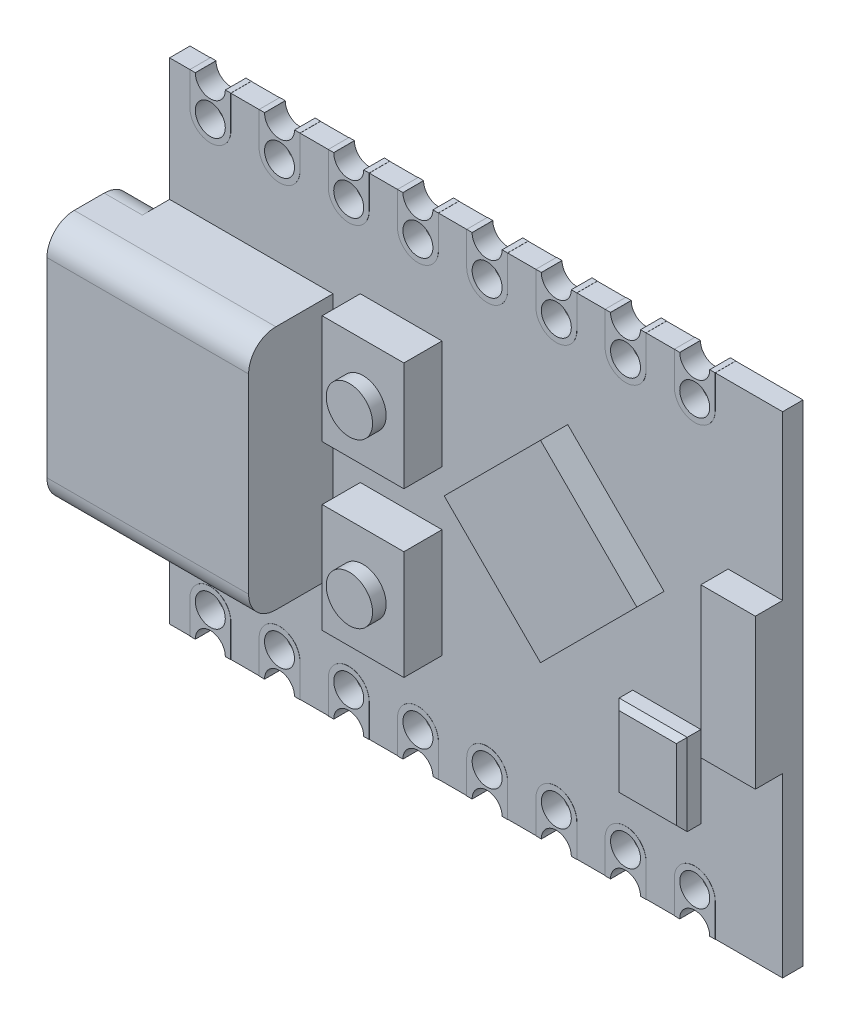
SolidWorks part; units mm, degrees
ref_plane "Plano frontal" through (0, 0, 0) normal (0, 0, 1) x (1, 0, 0)
ref_plane "Plano superior" through (0, 0, 0) normal (0, 1, 0) x (1, 0, 0)
ref_plane "Plano direito" through (0, 0, 0) normal (1, 0, 0) x (0, 0, -1)
sketch "Esboço1" plane through (0, 0, 0) normal (0, 0, 1) x (1, 0, 0)
  line L1 (-22.5, 18) -> (0, 18)
  line L2 (-22.5, 18) -> (-22.5, 0)
  line L3 (-22.5, 0) -> (0, 0)
  line L4 (0, 18) -> (0, 0)
  dimension "D1" = 18
  dimension "D2" = 22.5
extrude "PCI" add sketch "Esboço1" along normal blind 0.75
sketch "Esboço2" plane through (0, 0, 0.75) normal (0, 0, 1) x (1, 0, 0)
  line L0 (-11.4211, 10.1145) -> (-7.8855, 13.65)
  line L1 (-11.4211, 10.1145) -> (-7.8855, 6.5789)
  line L2 (-7.8855, 13.65) -> (-4.35, 10.1145)
  line L3 (-7.8855, 6.5789) -> (-4.35, 10.1145)
  line L4 (0, 0) -> (0, 18) construction
  line L5 (0, 18) -> (-22.5, 18) construction
  dimension "D1" = 45
  dimension "D2" = 4.35
  dimension "D3" = 4.35
  dimension "D4" = 5
extrude "ESP32" add sketch "Esboço2" along normal blind 1
sketch "Esboço3" plane through (0, 0, 0.75) normal (0, 0, 1) x (1, 0, 0)
  line L0 (-22.5, 18) -> (-22.5, 0) construction
  line L1 (-16.5, 13.5) -> (-23.9, 13.5)
  line L2 (-16.5, 13.5) -> (-16.5, 4.5)
  line L3 (-16.5, 4.5) -> (-23.9, 4.5)
  line L4 (-23.9, 13.5) -> (-23.9, 4.5)
  line L5 (-22.5, 9) -> (0, 9) construction
  line L6 (0, 0) -> (0, 18) construction
  dimension "D1" = 1.4
  dimension "D2" = 7.4
  dimension "D3" = 4.5
  dimension "D4" = 9
extrude "USB-C" add sketch "Esboço3" along normal blind 3.1
fillet "Arredondamento inferior USB" radius 1 2 edges at (-23.2, 13.5, 0.75) (-23.2, 4.5, 0.75)
fillet "Arredondamento Superior USB" radius 1 2 edges at (-20.2, 13.5, 3.85) (-20.2, 4.5, 3.85)
sketch "Esboço8" plane through (-23.9, 0, 0) normal (-1, 0, 0) x (0, 0, 1)
  line L0 (1.05, 12.5) -> (1.05, 5.5)
  line L1 (1.75, 4.8) -> (2.85, 4.8)
  line L2 (3.55, 5.5) -> (3.55, 12.5)
  line L3 (2.85, 13.2) -> (1.75, 13.2)
  line L4 (2.85, 13.5) -> (1.75, 13.5) construction
  line L5 (3.85, 12.5) -> (3.85, 5.5) construction
  arc A0 (1.75, 13.2) -> (1.05, 12.5) centre (1.75, 12.5) ccw
  arc A1 (1.05, 5.5) -> (1.75, 4.8) centre (1.75, 5.5) ccw
  arc A2 (2.85, 4.8) -> (3.55, 5.5) centre (2.85, 5.5) ccw
  arc A3 (3.55, 12.5) -> (2.85, 13.2) centre (2.85, 12.5) ccw
  dimension "D1" = 0.7
  dimension "D2" = 0.3
  dimension "D3" = 2.8
  dimension "D4" = 0.3
  dimension "D5" = 8.7
extrude "Furo USB" cut sketch "Esboço8" against normal blind 3.1
sketch "Esboço9" plane through (-23.9, 0, 0) normal (-1, 0, 0) x (0, 0, 1)
  line L0 (2.3, 13.2) -> (2.3, 4.8) construction
  line L1 (2.85, 13.2) -> (1.75, 13.2) construction
  line L2 (1.75, 4.8) -> (2.85, 4.8) construction
  line L3 (1.925, 5.4) -> (2.675, 5.4)
  line L4 (1.925, 5.4) -> (1.925, 12.6)
  line L5 (1.925, 12.6) -> (2.675, 12.6)
  line L6 (2.675, 5.4) -> (2.675, 12.6)
  line L7 (1.925, 5.4) -> (2.675, 12.6) construction
  line L8 (1.925, 12.6) -> (2.675, 5.4) construction
  point P4 (2.3, 9)
  dimension "D1" = 0.6
  dimension "D2" = 0.6
  dimension "D3" = 0.75
extrude "ConexaoUSB" add sketch "Esboço9" against normal up to next from offset 0.5 offset against normal yes
sketch "Esboço10" plane through (0, 0, 0.75) normal (0, 0, 1) x (1, 0, 0)
  line L0 (-22.5, 0) -> (0, 0) construction
  line L1 (-22.5, 4.5) -> (-22.5, 0) construction
  line L2 (-21, 1.2) -> (-21, -0.7241) construction
  line L3 (-21, 16.8) -> (-21, 18.7241) construction
  line L4 (0, 9) -> (-28.3512, 9) construction
  line L5 (0, 0) -> (0, 18) construction
  circle A0 centre (-21, 1.2) radius 0.55
  circle A1 centre (-21, 0) radius 0.55
  circle A2 centre (-18.46, 1.2) radius 0.55
  circle A3 centre (-18.46, 0) radius 0.55
  circle A4 centre (-15.92, 1.2) radius 0.55
  circle A5 centre (-15.92, 0) radius 0.55
  circle A6 centre (-13.38, 1.2) radius 0.55
  circle A7 centre (-13.38, 0) radius 0.55
  circle A8 centre (-10.84, 1.2) radius 0.55
  circle A9 centre (-10.84, 0) radius 0.55
  circle A10 centre (-8.3, 1.2) radius 0.55
  circle A11 centre (-8.3, 0) radius 0.55
  circle A12 centre (-5.76, 1.2) radius 0.55
  circle A13 centre (-5.76, 0) radius 0.55
  circle A14 centre (-3.22, 1.2) radius 0.55
  circle A15 centre (-3.22, 0) radius 0.55
  circle A16 centre (-3.22, 18) radius 0.55
  circle A17 centre (-3.22, 16.8) radius 0.55
  circle A18 centre (-5.76, 18) radius 0.55
  circle A19 centre (-5.76, 16.8) radius 0.55
  circle A20 centre (-8.3, 18) radius 0.55
  circle A21 centre (-8.3, 16.8) radius 0.55
  circle A22 centre (-10.84, 18) radius 0.55
  circle A23 centre (-10.84, 16.8) radius 0.55
  circle A24 centre (-13.38, 18) radius 0.55
  circle A25 centre (-13.38, 16.8) radius 0.55
  circle A26 centre (-15.92, 18) radius 0.55
  circle A27 centre (-15.92, 16.8) radius 0.55
  circle A28 centre (-18.46, 18) radius 0.55
  circle A29 centre (-18.46, 16.8) radius 0.55
  circle A30 centre (-21, 18) radius 0.55
  circle A31 centre (-21, 16.8) radius 0.55
  dimension "D1" = 1.2
  dimension "D2" = 1.1
  dimension "D7" = 2.54
  dimension "D3" = 0
  dimension "D4" = 1.5
  dimension "D5" = 8
extrude "FurosPCB" cut sketch "Esboço10" against normal up to next (0.75 mm away)
sketch "Esboço11" plane through (0, 0, 0.75) normal (0, 0, 1) x (1, 0, 0)
  line L0 (-21.75, 1.2) -> (-21.75, 0)
  line L1 (-20.25, 1.2) -> (-20.25, 0)
  line L2 (-17.71, 1.2) -> (-17.71, 0)
  line L4 (-21.75, 0) -> (-21.55, 0)
  line L5 (-20.45, 0) -> (-20.25, 0)
  line L6 (-17.91, 0) -> (-17.71, 0)
  line L7 (-19.21, 1.2) -> (-19.21, 0)
  line L8 (-19.21, 0) -> (-19.01, 0)
  line L9 (-15.17, 1.2) -> (-15.17, 0)
  line L10 (-15.37, 0) -> (-15.17, 0)
  line L11 (-16.67, 1.2) -> (-16.67, 0)
  line L12 (-16.67, 0) -> (-16.47, 0)
  line L13 (-12.63, 1.2) -> (-12.63, 0)
  line L14 (-12.83, 0) -> (-12.63, 0)
  line L15 (-14.13, 1.2) -> (-14.13, 0)
  line L16 (-14.13, 0) -> (-13.93, 0)
  line L17 (-10.09, 1.2) -> (-10.09, 0)
  line L18 (-10.29, 0) -> (-10.09, 0)
  line L19 (-11.59, 1.2) -> (-11.59, 0)
  line L20 (-11.59, 0) -> (-11.39, 0)
  line L21 (-7.55, 1.2) -> (-7.55, 0)
  line L22 (-7.75, 0) -> (-7.55, 0)
  line L23 (-9.05, 1.2) -> (-9.05, 0)
  line L24 (-9.05, 0) -> (-8.85, 0)
  line L25 (-5.01, 1.2) -> (-5.01, 0)
  line L26 (-5.21, 0) -> (-5.01, 0)
  line L27 (-6.51, 1.2) -> (-6.51, 0)
  line L28 (-6.51, 0) -> (-6.31, 0)
  line L29 (-2.47, 1.2) -> (-2.47, 0)
  line L30 (-2.67, 0) -> (-2.47, 0)
  line L31 (-3.97, 1.2) -> (-3.97, 0)
  line L32 (-3.97, 0) -> (-3.77, 0)
  line L33 (0, 9) -> (-27.4378, 9) construction
  line L34 (0, 0) -> (0, 18) construction
  line L35 (-3.97, 18) -> (-3.77, 18)
  line L36 (-3.97, 16.8) -> (-3.97, 18)
  line L37 (-2.67, 18) -> (-2.47, 18)
  line L38 (-2.47, 16.8) -> (-2.47, 18)
  line L39 (-6.51, 18) -> (-6.31, 18)
  line L40 (-6.51, 16.8) -> (-6.51, 18)
  line L41 (-5.21, 18) -> (-5.01, 18)
  line L42 (-5.01, 16.8) -> (-5.01, 18)
  line L43 (-9.05, 18) -> (-8.85, 18)
  line L44 (-9.05, 16.8) -> (-9.05, 18)
  line L45 (-7.75, 18) -> (-7.55, 18)
  line L46 (-7.55, 16.8) -> (-7.55, 18)
  line L47 (-11.59, 18) -> (-11.39, 18)
  line L48 (-11.59, 16.8) -> (-11.59, 18)
  line L49 (-10.29, 18) -> (-10.09, 18)
  line L50 (-10.09, 16.8) -> (-10.09, 18)
  line L51 (-14.13, 18) -> (-13.93, 18)
  line L52 (-14.13, 16.8) -> (-14.13, 18)
  line L53 (-12.83, 18) -> (-12.63, 18)
  line L54 (-12.63, 16.8) -> (-12.63, 18)
  line L55 (-16.67, 18) -> (-16.47, 18)
  line L56 (-16.67, 16.8) -> (-16.67, 18)
  line L57 (-15.37, 18) -> (-15.17, 18)
  line L58 (-15.17, 16.8) -> (-15.17, 18)
  line L59 (-19.21, 18) -> (-19.01, 18)
  line L60 (-19.21, 16.8) -> (-19.21, 18)
  line L61 (-17.91, 18) -> (-17.71, 18)
  line L62 (-20.45, 18) -> (-20.25, 18)
  line L63 (-21.75, 18) -> (-21.55, 18)
  line L64 (-17.71, 16.8) -> (-17.71, 18)
  line L65 (-20.25, 16.8) -> (-20.25, 18)
  line L66 (-21.75, 16.8) -> (-21.75, 18)
  arc A9 (-20.45, 0) -> (-21.55, 0) centre (-21, 0) ccw construction
  circle A10 centre (-21, 1.2) radius 0.75
  arc A11 (-20.25, 1.2) -> (-21.75, 1.2) centre (-21, 1.2) ccw
  arc A12 (-20.45, 0) -> (-21.55, 0) centre (-21, 0) ccw
  circle A13 centre (-21, 1.2) radius 0.55 construction
  circle A14 centre (-21, 1.2) radius 0.55
  arc A15 (-17.91, 0) -> (-19.01, 0) centre (-18.46, 0) ccw
  circle A16 centre (-18.46, 1.2) radius 0.55
  arc A17 (-17.71, 1.2) -> (-19.21, 1.2) centre (-18.46, 1.2) ccw
  arc A18 (-15.37, 0) -> (-16.47, 0) centre (-15.92, 0) ccw
  circle A19 centre (-15.92, 1.2) radius 0.55
  arc A20 (-15.17, 1.2) -> (-16.67, 1.2) centre (-15.92, 1.2) ccw
  arc A21 (-12.83, 0) -> (-13.93, 0) centre (-13.38, 0) ccw
  circle A22 centre (-13.38, 1.2) radius 0.55
  arc A23 (-12.63, 1.2) -> (-14.13, 1.2) centre (-13.38, 1.2) ccw
  arc A24 (-10.29, 0) -> (-11.39, 0) centre (-10.84, 0) ccw
  circle A25 centre (-10.84, 1.2) radius 0.55
  arc A26 (-10.09, 1.2) -> (-11.59, 1.2) centre (-10.84, 1.2) ccw
  arc A27 (-7.75, 0) -> (-8.85, 0) centre (-8.3, 0) ccw
  circle A28 centre (-8.3, 1.2) radius 0.55
  arc A29 (-7.55, 1.2) -> (-9.05, 1.2) centre (-8.3, 1.2) ccw
  arc A30 (-5.21, 0) -> (-6.31, 0) centre (-5.76, 0) ccw
  circle A31 centre (-5.76, 1.2) radius 0.55
  arc A32 (-5.01, 1.2) -> (-6.51, 1.2) centre (-5.76, 1.2) ccw
  arc A33 (-2.67, 0) -> (-3.77, 0) centre (-3.22, 0) ccw
  circle A34 centre (-3.22, 1.2) radius 0.55
  arc A35 (-2.47, 1.2) -> (-3.97, 1.2) centre (-3.22, 1.2) ccw
  arc A36 (-2.47, 16.8) -> (-3.97, 16.8) centre (-3.22, 16.8) cw
  circle A37 centre (-3.22, 16.8) radius 0.55
  arc A38 (-2.67, 18) -> (-3.77, 18) centre (-3.22, 18) cw
  arc A39 (-5.01, 16.8) -> (-6.51, 16.8) centre (-5.76, 16.8) cw
  circle A40 centre (-5.76, 16.8) radius 0.55
  arc A41 (-5.21, 18) -> (-6.31, 18) centre (-5.76, 18) cw
  arc A42 (-7.55, 16.8) -> (-9.05, 16.8) centre (-8.3, 16.8) cw
  circle A43 centre (-8.3, 16.8) radius 0.55
  arc A44 (-7.75, 18) -> (-8.85, 18) centre (-8.3, 18) cw
  arc A45 (-10.09, 16.8) -> (-11.59, 16.8) centre (-10.84, 16.8) cw
  circle A46 centre (-10.84, 16.8) radius 0.55
  arc A47 (-10.29, 18) -> (-11.39, 18) centre (-10.84, 18) cw
  arc A48 (-12.63, 16.8) -> (-14.13, 16.8) centre (-13.38, 16.8) cw
  circle A49 centre (-13.38, 16.8) radius 0.55
  arc A50 (-12.83, 18) -> (-13.93, 18) centre (-13.38, 18) cw
  arc A51 (-15.17, 16.8) -> (-16.67, 16.8) centre (-15.92, 16.8) cw
  circle A52 centre (-15.92, 16.8) radius 0.55
  arc A53 (-15.37, 18) -> (-16.47, 18) centre (-15.92, 18) cw
  arc A54 (-17.71, 16.8) -> (-19.21, 16.8) centre (-18.46, 16.8) cw
  circle A55 centre (-18.46, 16.8) radius 0.55
  arc A56 (-17.91, 18) -> (-19.01, 18) centre (-18.46, 18) cw
  circle A57 centre (-21, 16.8) radius 0.55
  arc A58 (-20.45, 18) -> (-21.55, 18) centre (-21, 18) cw
  arc A59 (-20.25, 16.8) -> (-21.75, 16.8) centre (-21, 16.8) cw
  dimension "D1" = 0.2
  dimension "D2" = 8
extrude "PADs" add sketch "Esboço11" along normal blind 0.005
sketch "Esboço13" plane through (0, 0, 0) normal (0, 0, -1) x (-1, 0, 0)
  line L0 (22.5, 0) -> (21.55, 0) construction
  line L1 (20.45, 0) -> (19.01, 0) construction
  line L2 (21.75, 0) -> (21.55, 0)
  line L3 (20.45, 0) -> (20.25, 0)
  line L4 (20.25, 1.2) -> (20.25, 0)
  line L5 (21.75, 1.2) -> (21.75, 0)
  line L6 (19.21, 1.2) -> (19.21, 0)
  line L7 (19.21, 0) -> (19.01, 0)
  line L8 (17.91, 0) -> (17.71, 0)
  line L9 (17.71, 1.2) -> (17.71, 0)
  line L10 (16.67, 1.2) -> (16.67, 0)
  line L11 (16.67, 0) -> (16.47, 0)
  line L12 (15.37, 0) -> (15.17, 0)
  line L13 (15.17, 1.2) -> (15.17, 0)
  line L14 (14.13, 1.2) -> (14.13, 0)
  line L15 (14.13, 0) -> (13.93, 0)
  line L16 (12.83, 0) -> (12.63, 0)
  line L17 (12.63, 1.2) -> (12.63, 0)
  line L18 (11.59, 1.2) -> (11.59, 0)
  line L19 (11.59, 0) -> (11.39, 0)
  line L20 (10.29, 0) -> (10.09, 0)
  line L21 (10.09, 1.2) -> (10.09, 0)
  line L22 (9.05, 1.2) -> (9.05, 0)
  line L23 (9.05, 0) -> (8.85, 0)
  line L24 (7.75, 0) -> (7.55, 0)
  line L25 (7.55, 1.2) -> (7.55, 0)
  line L26 (6.51, 1.2) -> (6.51, 0)
  line L27 (6.51, 0) -> (6.31, 0)
  line L28 (5.21, 0) -> (5.01, 0)
  line L29 (5.01, 1.2) -> (5.01, 0)
  line L30 (3.97, 1.2) -> (3.97, 0)
  line L31 (3.97, 0) -> (3.77, 0)
  line L32 (2.67, 0) -> (2.47, 0)
  line L33 (2.47, 1.2) -> (2.47, 0)
  line L34 (0, 9) -> (22.5, 9) construction
  line L35 (0, 0) -> (0, 18) construction
  line L36 (22.5, 18) -> (22.5, 0) construction
  line L37 (2.47, 16.8) -> (2.47, 18)
  line L38 (2.67, 18) -> (2.47, 18)
  line L39 (3.97, 18) -> (3.77, 18)
  line L40 (3.97, 16.8) -> (3.97, 18)
  line L41 (5.01, 16.8) -> (5.01, 18)
  line L42 (5.21, 18) -> (5.01, 18)
  line L43 (6.51, 18) -> (6.31, 18)
  line L44 (6.51, 16.8) -> (6.51, 18)
  line L45 (7.55, 16.8) -> (7.55, 18)
  line L46 (7.75, 18) -> (7.55, 18)
  line L47 (9.05, 18) -> (8.85, 18)
  line L48 (9.05, 16.8) -> (9.05, 18)
  line L49 (10.09, 16.8) -> (10.09, 18)
  line L50 (10.29, 18) -> (10.09, 18)
  line L51 (11.59, 18) -> (11.39, 18)
  line L52 (11.59, 16.8) -> (11.59, 18)
  line L53 (12.63, 16.8) -> (12.63, 18)
  line L54 (12.83, 18) -> (12.63, 18)
  line L55 (14.13, 18) -> (13.93, 18)
  line L56 (14.13, 16.8) -> (14.13, 18)
  line L57 (15.17, 16.8) -> (15.17, 18)
  line L58 (15.37, 18) -> (15.17, 18)
  line L59 (16.67, 18) -> (16.47, 18)
  line L60 (16.67, 16.8) -> (16.67, 18)
  line L61 (17.71, 16.8) -> (17.71, 18)
  line L62 (17.91, 18) -> (17.71, 18)
  line L63 (19.21, 18) -> (19.01, 18)
  line L64 (19.21, 16.8) -> (19.21, 18)
  line L65 (21.75, 16.8) -> (21.75, 18)
  line L66 (20.25, 16.8) -> (20.25, 18)
  line L67 (20.45, 18) -> (20.25, 18)
  line L68 (21.75, 18) -> (21.55, 18)
  circle A0 centre (21, 1.2) radius 0.55 construction
  arc A1 (21.55, 0) -> (20.45, 0) centre (21, 0) ccw construction
  circle A2 centre (21, 1.2) radius 0.55
  arc A3 (21.55, 0) -> (20.45, 0) centre (21, 0) ccw
  arc A4 (21.75, 1.2) -> (20.25, 1.2) centre (21, 1.2) ccw
  circle A5 centre (21, 1.2) radius 0.75 construction
  arc A6 (19.01, 0) -> (17.91, 0) centre (18.46, 0) ccw
  arc A7 (19.21, 1.2) -> (17.71, 1.2) centre (18.46, 1.2) ccw
  circle A8 centre (18.46, 1.2) radius 0.55
  arc A9 (16.47, 0) -> (15.37, 0) centre (15.92, 0) ccw
  arc A10 (16.67, 1.2) -> (15.17, 1.2) centre (15.92, 1.2) ccw
  circle A11 centre (15.92, 1.2) radius 0.55
  arc A12 (13.93, 0) -> (12.83, 0) centre (13.38, 0) ccw
  arc A13 (14.13, 1.2) -> (12.63, 1.2) centre (13.38, 1.2) ccw
  circle A14 centre (13.38, 1.2) radius 0.55
  arc A15 (11.39, 0) -> (10.29, 0) centre (10.84, 0) ccw
  arc A16 (11.59, 1.2) -> (10.09, 1.2) centre (10.84, 1.2) ccw
  circle A17 centre (10.84, 1.2) radius 0.55
  arc A18 (8.85, 0) -> (7.75, 0) centre (8.3, 0) ccw
  arc A19 (9.05, 1.2) -> (7.55, 1.2) centre (8.3, 1.2) ccw
  circle A20 centre (8.3, 1.2) radius 0.55
  arc A21 (6.31, 0) -> (5.21, 0) centre (5.76, 0) ccw
  arc A22 (6.51, 1.2) -> (5.01, 1.2) centre (5.76, 1.2) ccw
  circle A23 centre (5.76, 1.2) radius 0.55
  arc A24 (3.77, 0) -> (2.67, 0) centre (3.22, 0) ccw
  arc A25 (3.97, 1.2) -> (2.47, 1.2) centre (3.22, 1.2) ccw
  circle A26 centre (3.22, 1.2) radius 0.55
  circle A27 centre (3.22, 16.8) radius 0.55
  arc A28 (3.97, 16.8) -> (2.47, 16.8) centre (3.22, 16.8) cw
  arc A29 (3.77, 18) -> (2.67, 18) centre (3.22, 18) cw
  circle A30 centre (5.76, 16.8) radius 0.55
  arc A31 (6.51, 16.8) -> (5.01, 16.8) centre (5.76, 16.8) cw
  arc A32 (6.31, 18) -> (5.21, 18) centre (5.76, 18) cw
  circle A33 centre (8.3, 16.8) radius 0.55
  arc A34 (9.05, 16.8) -> (7.55, 16.8) centre (8.3, 16.8) cw
  arc A35 (8.85, 18) -> (7.75, 18) centre (8.3, 18) cw
  circle A36 centre (10.84, 16.8) radius 0.55
  arc A37 (11.59, 16.8) -> (10.09, 16.8) centre (10.84, 16.8) cw
  arc A38 (11.39, 18) -> (10.29, 18) centre (10.84, 18) cw
  circle A39 centre (13.38, 16.8) radius 0.55
  arc A40 (14.13, 16.8) -> (12.63, 16.8) centre (13.38, 16.8) cw
  arc A41 (13.93, 18) -> (12.83, 18) centre (13.38, 18) cw
  circle A42 centre (15.92, 16.8) radius 0.55
  arc A43 (16.67, 16.8) -> (15.17, 16.8) centre (15.92, 16.8) cw
  arc A44 (16.47, 18) -> (15.37, 18) centre (15.92, 18) cw
  circle A45 centre (18.46, 16.8) radius 0.55
  arc A46 (19.21, 16.8) -> (17.71, 16.8) centre (18.46, 16.8) cw
  arc A47 (19.01, 18) -> (17.91, 18) centre (18.46, 18) cw
  arc A48 (21.75, 16.8) -> (20.25, 16.8) centre (21, 16.8) cw
  arc A49 (21.55, 18) -> (20.45, 18) centre (21, 18) cw
  circle A50 centre (21, 16.8) radius 0.55
  dimension "D1" = 0.2
  dimension "D2" = 8
extrude "InferiorPads" add sketch "Esboço13" along normal blind 0.005
sketch "Esboço14" plane through (0, 18, 0) normal (0, 1, 0) x (1, 0, 0)
  line L0 (-21.75, 0.005) -> (-21.75, -0.755)
  line L1 (-21.75, -0.755) -> (-21.55, -0.755)
  line L2 (-21.55, -0.755) -> (-21.55, 0.005)
  line L3 (-21.55, 0.005) -> (-21.75, 0.005)
  line L4 (-20.45, 0.005) -> (-20.25, 0)
  line L5 (-20.25, 0) -> (-20.25, -0.755)
  line L6 (-20.25, -0.755) -> (-20.45, -0.755)
  line L7 (-20.45, -0.755) -> (-20.45, 0.005)
  line L8 (-19.21, 0.005) -> (-19.21, -0.755)
  line L9 (-19.01, 0.005) -> (-19.21, 0.005)
  line L10 (-19.01, -0.755) -> (-19.01, 0.005)
  line L11 (-19.21, -0.755) -> (-19.01, -0.755)
  line L12 (-17.91, -0.755) -> (-17.91, 0.005)
  line L13 (-17.91, 0.005) -> (-17.71, 0)
  line L14 (-17.71, 0) -> (-17.71, -0.755)
  line L15 (-17.71, -0.755) -> (-17.91, -0.755)
  line L16 (-16.67, 0.005) -> (-16.67, -0.755)
  line L17 (-16.47, 0.005) -> (-16.67, 0.005)
  line L18 (-16.47, -0.755) -> (-16.47, 0.005)
  line L19 (-16.67, -0.755) -> (-16.47, -0.755)
  line L20 (-15.37, -0.755) -> (-15.37, 0.005)
  line L21 (-15.37, 0.005) -> (-15.17, 0)
  line L22 (-15.17, 0) -> (-15.17, -0.755)
  line L23 (-15.17, -0.755) -> (-15.37, -0.755)
  line L24 (-14.13, 0.005) -> (-14.13, -0.755)
  line L25 (-13.93, 0.005) -> (-14.13, 0.005)
  line L26 (-13.93, -0.755) -> (-13.93, 0.005)
  line L27 (-14.13, -0.755) -> (-13.93, -0.755)
  line L28 (-12.83, -0.755) -> (-12.83, 0.005)
  line L29 (-12.83, 0.005) -> (-12.63, 0)
  line L30 (-12.63, 0) -> (-12.63, -0.755)
  line L31 (-12.63, -0.755) -> (-12.83, -0.755)
  line L32 (-11.59, 0.005) -> (-11.59, -0.755)
  line L33 (-11.39, 0.005) -> (-11.59, 0.005)
  line L34 (-11.39, -0.755) -> (-11.39, 0.005)
  line L35 (-11.59, -0.755) -> (-11.39, -0.755)
  line L36 (-10.29, -0.755) -> (-10.29, 0.005)
  line L37 (-10.29, 0.005) -> (-10.09, 0)
  line L38 (-10.09, 0) -> (-10.09, -0.755)
  line L39 (-10.09, -0.755) -> (-10.29, -0.755)
  line L40 (-9.05, 0.005) -> (-9.05, -0.755)
  line L41 (-8.85, 0.005) -> (-9.05, 0.005)
  line L42 (-8.85, -0.755) -> (-8.85, 0.005)
  line L43 (-9.05, -0.755) -> (-8.85, -0.755)
  line L44 (-7.75, -0.755) -> (-7.75, 0.005)
  line L45 (-7.75, 0.005) -> (-7.55, 0)
  line L46 (-7.55, 0) -> (-7.55, -0.755)
  line L47 (-7.55, -0.755) -> (-7.75, -0.755)
  line L48 (-6.51, 0.005) -> (-6.51, -0.755)
  line L49 (-6.31, 0.005) -> (-6.51, 0.005)
  line L50 (-6.31, -0.755) -> (-6.31, 0.005)
  line L51 (-6.51, -0.755) -> (-6.31, -0.755)
  line L52 (-5.21, -0.755) -> (-5.21, 0.005)
  line L53 (-5.21, 0.005) -> (-5.01, 0)
  line L54 (-5.01, 0) -> (-5.01, -0.755)
  line L55 (-5.01, -0.755) -> (-5.21, -0.755)
  line L56 (-3.97, 0.005) -> (-3.97, -0.755)
  line L57 (-3.77, 0.005) -> (-3.97, 0.005)
  line L58 (-3.77, -0.755) -> (-3.77, 0.005)
  line L59 (-3.97, -0.755) -> (-3.77, -0.755)
  line L60 (-2.67, -0.755) -> (-2.67, 0.005)
  line L61 (-2.67, 0.005) -> (-2.47, 0)
  line L62 (-2.47, 0) -> (-2.47, -0.755)
  line L63 (-2.47, -0.755) -> (-2.67, -0.755)
  dimension "D1" = 8
extrude "PADEx" add sketch "Esboço14" along normal blind 0.005
sketch "Esboço16" plane through (0, 0, 0) normal (0, -1, 0) x (1, 0, 0)
  line L0 (-21.75, 0.755) -> (-21.55, 0.755) construction
  line L1 (-21.75, 0.755) -> (-21.55, 0.755)
  line L2 (-21.75, 0.755) -> (-21.75, -0.005)
  line L3 (-21.75, -0.005) -> (-21.55, -0.005)
  line L4 (-21.55, 0.755) -> (-21.55, -0.005)
  line L5 (-20.45, -0.005) -> (-20.25, -0.005)
  line L6 (-20.45, -0.005) -> (-20.45, 0.755)
  line L7 (-20.45, 0.755) -> (-20.25, 0.755)
  line L8 (-20.25, -0.005) -> (-20.25, 0.755)
  line L9 (-21.75, 0.755) -> (-21.75, 0.75) construction
  line L10 (-17.71, -0.005) -> (-17.71, 0.755)
  line L11 (-17.91, -0.005) -> (-17.91, 0.755)
  line L12 (-17.91, -0.005) -> (-17.71, -0.005)
  line L13 (-17.91, 0.755) -> (-17.71, 0.755)
  line L14 (-19.21, 0.755) -> (-19.01, 0.755)
  line L15 (-19.21, 0.755) -> (-19.21, -0.005)
  line L16 (-19.21, -0.005) -> (-19.01, -0.005)
  line L17 (-19.01, 0.755) -> (-19.01, -0.005)
  line L18 (-15.17, -0.005) -> (-15.17, 0.755)
  line L19 (-15.37, -0.005) -> (-15.37, 0.755)
  line L20 (-15.37, -0.005) -> (-15.17, -0.005)
  line L21 (-15.37, 0.755) -> (-15.17, 0.755)
  line L22 (-16.67, 0.755) -> (-16.47, 0.755)
  line L23 (-16.67, 0.755) -> (-16.67, -0.005)
  line L24 (-16.67, -0.005) -> (-16.47, -0.005)
  line L25 (-16.47, 0.755) -> (-16.47, -0.005)
  line L26 (-12.63, -0.005) -> (-12.63, 0.755)
  line L27 (-12.83, -0.005) -> (-12.83, 0.755)
  line L28 (-12.83, -0.005) -> (-12.63, -0.005)
  line L29 (-12.83, 0.755) -> (-12.63, 0.755)
  line L30 (-14.13, 0.755) -> (-13.93, 0.755)
  line L31 (-14.13, 0.755) -> (-14.13, -0.005)
  line L32 (-14.13, -0.005) -> (-13.93, -0.005)
  line L33 (-13.93, 0.755) -> (-13.93, -0.005)
  line L34 (-10.09, -0.005) -> (-10.09, 0.755)
  line L35 (-10.29, -0.005) -> (-10.29, 0.755)
  line L36 (-10.29, -0.005) -> (-10.09, -0.005)
  line L37 (-10.29, 0.755) -> (-10.09, 0.755)
  line L38 (-11.59, 0.755) -> (-11.39, 0.755)
  line L39 (-11.59, 0.755) -> (-11.59, -0.005)
  line L40 (-11.59, -0.005) -> (-11.39, -0.005)
  line L41 (-11.39, 0.755) -> (-11.39, -0.005)
  line L42 (-7.55, -0.005) -> (-7.55, 0.755)
  line L43 (-7.75, -0.005) -> (-7.75, 0.755)
  line L44 (-7.75, -0.005) -> (-7.55, -0.005)
  line L45 (-7.75, 0.755) -> (-7.55, 0.755)
  line L46 (-9.05, 0.755) -> (-8.85, 0.755)
  line L47 (-9.05, 0.755) -> (-9.05, -0.005)
  line L48 (-9.05, -0.005) -> (-8.85, -0.005)
  line L49 (-8.85, 0.755) -> (-8.85, -0.005)
  line L50 (-5.01, -0.005) -> (-5.01, 0.755)
  line L51 (-5.21, -0.005) -> (-5.21, 0.755)
  line L52 (-5.21, -0.005) -> (-5.01, -0.005)
  line L53 (-5.21, 0.755) -> (-5.01, 0.755)
  line L54 (-6.51, 0.755) -> (-6.31, 0.755)
  line L55 (-6.51, 0.755) -> (-6.51, -0.005)
  line L56 (-6.51, -0.005) -> (-6.31, -0.005)
  line L57 (-6.31, 0.755) -> (-6.31, -0.005)
  line L58 (-2.47, -0.005) -> (-2.47, 0.755)
  line L59 (-2.67, -0.005) -> (-2.67, 0.755)
  line L60 (-2.67, -0.005) -> (-2.47, -0.005)
  line L61 (-2.67, 0.755) -> (-2.47, 0.755)
  line L62 (-3.97, 0.755) -> (-3.77, 0.755)
  line L63 (-3.97, 0.755) -> (-3.97, -0.005)
  line L64 (-3.97, -0.005) -> (-3.77, -0.005)
  line L65 (-3.77, 0.755) -> (-3.77, -0.005)
  dimension "D1" = 8
extrude "PADEx1" add sketch "Esboço16" along normal blind 0.005
sketch "Esboço17" plane through (0, 0, 0.75) normal (0, 0, 1) x (1, 0, 0)
  line L0 (0, 18) -> (-2.47, 18) construction
  line L1 (-2, 12) -> (0, 12)
  line L2 (-2, 12) -> (-2, 6.5)
  line L3 (-2, 6.5) -> (0, 6.5)
  line L4 (0, 12) -> (0, 6.5)
  line L5 (0, 0) -> (0, 18) construction
  dimension "D1" = 6
  dimension "D2" = 5.5
  dimension "D3" = 2
extrude "Antena" add sketch "Esboço17" along normal blind 1
sketch "Esboço18" plane through (0, 0, 0.75) normal (0, 0, 1) x (1, 0, 0)
  line L0 (-16.5, 4.5) -> (-16.5, 13.5) construction
  line L1 (-15.5, 14) -> (-12.5, 14)
  line L2 (-15.5, 14) -> (-15.5, 10)
  line L3 (-15.5, 10) -> (-12.5, 10)
  line L4 (-12.5, 14) -> (-12.5, 10)
  line L5 (-15.5, 8) -> (-12.5, 8)
  line L6 (-15.5, 8) -> (-15.5, 4)
  line L7 (-15.5, 4) -> (-12.5, 4)
  line L8 (-12.5, 8) -> (-12.5, 4)
  line L9 (-14.13, 18) -> (-15.17, 18) construction
  point P8 (-16.5, 9)
  dimension "D1" = 4
  dimension "D2" = 3
  dimension "D3" = 1
  dimension "D4" = 2
  dimension "D5" = 8
extrude "Buttons" add sketch "Esboço18" along normal blind 1.4
sketch "Esboço19" plane through (0, 0, 2.15) normal (0, 0, 1) x (1, 0, 0)
  line L0 (-12.5, 10) -> (-12.5, 14) construction
  line L2 (-12.5, 14) -> (-15.5, 14) construction
  line L4 (-12.5, 8) -> (-15.5, 8) construction
  line L5 (-12.5, 4) -> (-12.5, 8) construction
  circle A0 centre (-14, 6) radius 0.85
  circle A1 centre (-14, 12) radius 0.85
  point P6 (-14, 14)
  point P8 (-13.9585, 14)
  dimension "D1" = 1.7
  dimension "D2" = 1.5
  dimension "D3" = 2
  dimension "D4" = 2
  dimension "D5" = 1.5
extrude "Ressalto-extrusão12" add sketch "Esboço19" along normal blind 0.5
sketch "Esboço20" plane through (0, 0, 0.75) normal (0, 0, 1) x (1, 0, 0)
  line L0 (-5.01, 0) -> (-3.97, 0) construction
  line L1 (-5.5, 6.4) -> (-3, 6.4)
  line L2 (-5.5, 6.4) -> (-5.5, 3.4)
  line L3 (-5.5, 3.4) -> (-3, 3.4)
  line L4 (-3, 6.4) -> (-3, 3.4)
  line L5 (0, 0) -> (0, 6.5) construction
  dimension "D1" = 3
  dimension "D2" = 2.5
  dimension "D3" = 3.4
  dimension "D4" = 3
extrude "Ressalto-extrusão13" add sketch "Esboço20" along normal blind 0.7
chamfer "Chanfro1" distance 0.2 angle 45 4 edges at (-4.25, 6.4, 1.45) (-3, 4.9, 1.45) (-4.25, 3.4, 1.45) (-5.5, 4.9, 1.45)
